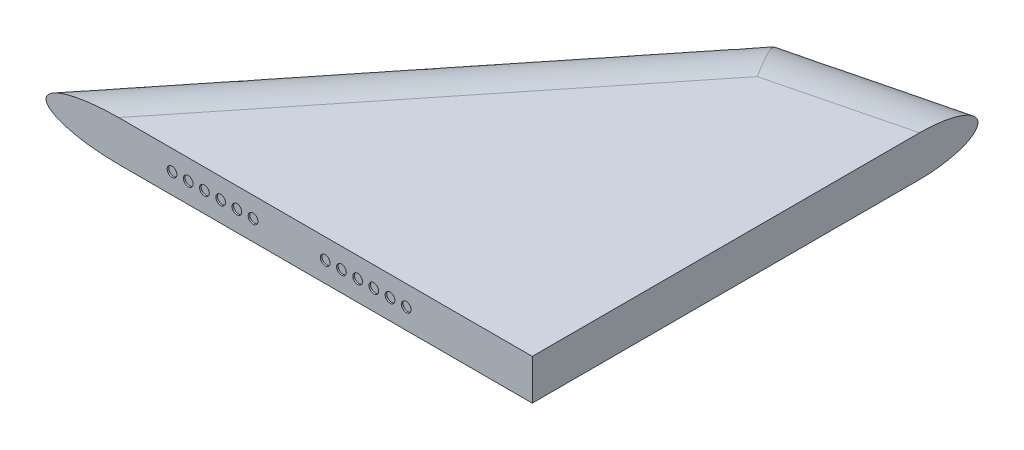
SolidWorks part; units mm, degrees
ref_plane "Front Plane" through (0, 0, 0) normal (0, 0, 1) x (1, 0, 0)
ref_plane "Top Plane" through (0, 0, 0) normal (0, 1, 0) x (1, 0, 0)
ref_plane "Right Plane" through (0, 0, 0) normal (1, 0, 0) x (0, 0, -1)
sketch "Sketch1" plane through (0, 0, 0) normal (0, 1, 0) x (1, 0, 0)
  line L0 (0, 0) -> (40, 50)
  line L1 (40, 50) -> (60, 55)
  line L2 (60, 55) -> (60, 0)
  line L3 (60, 0) -> (0, 0)
  dimension "D1" = 60
  dimension "D2" = 55
  dimension "D3" = 40
  dimension "D4" = 50
extrude "Boss-Extrude1" add sketch "Sketch1" along normal mid plane 5
fillet "Fillet3" radius 2.5 2 edges at (20, 2.5, -25) (50, 2.5, -52.5) second distance 7 first distance on face at (20, 0, -25) first distance on face at (50, 0, -52.5)
fillet "Fillet4" radius 2.5 2 edges at (20, -2.5, -25) (50, -2.5, -52.5) second distance 7 first distance on face at (15, -0.625, -18.75) first distance on face at (47.5, -0.625, -51.875)
sketch "Sketch2" plane through (0, 0, 0) normal (0, 0, 1) x (1, 0, 0)
  line L0 (13.95, 0) -> (46.05, 0) construction
  line L1 (30, 18.2316) -> (30, -20.3451) construction
  circle A0 centre (15.55, 0) radius 0.6
  circle A1 centre (17.55, 0) radius 0.6
  circle A2 centre (19.55, 0) radius 0.6
  circle A3 centre (21.55, 0) radius 0.6
  circle A4 centre (23.55, 0) radius 0.6
  circle A5 centre (25.55, 0) radius 0.6
  circle A6 centre (34.45, 0) radius 0.6
  circle A7 centre (36.45, 0) radius 0.6
  circle A8 centre (38.45, 0) radius 0.6
  circle A9 centre (40.45, 0) radius 0.6
  circle A10 centre (42.45, 0) radius 0.6
  circle A11 centre (44.45, 0) radius 0.6
  point P0 (30, 0)
  point P6 (30, 0)
  point P11 (0, 0)
  dimension "D3" = 1.2
  dimension "D1" = 30
  dimension "D2" = 32.1
  dimension "D4" = 1.6
  dimension "D5" = 6
  dimension "D6" = 2
extrude "Cut-Extrude1" cut sketch "Sketch2" against normal blind 0.2
